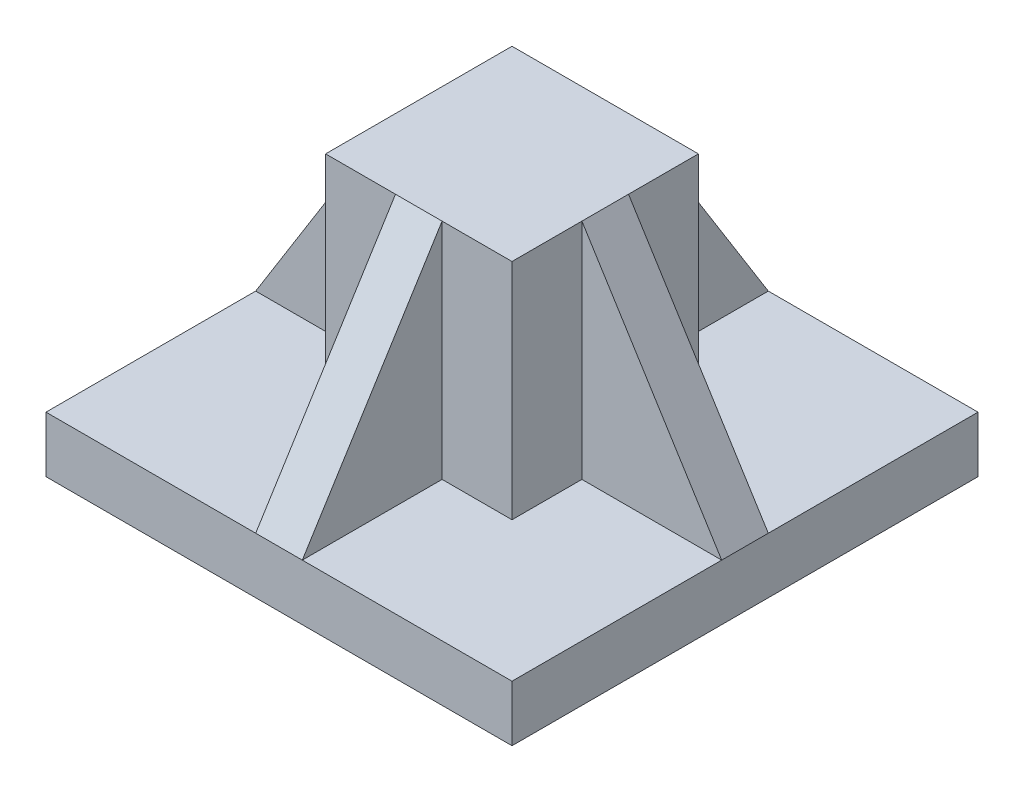
SolidWorks part; units mm, degrees
material "Thornel VCB-20 Carbon Cloth"
ref_plane "Front Plane" through (0, 0, 0) normal (0, 0, 1) x (1, 0, 0)
ref_plane "Top Plane" through (0, 0, 0) normal (0, 1, 0) x (1, 0, 0)
ref_plane "Right Plane" through (0, 0, 0) normal (1, 0, 0) x (0, 0, -1)
sketch "Sketch1" plane through (0, 0, 0) normal (0, 1, 0) x (1, 0, 0)
  line L1 (-20, 20) -> (20, 20)
  line L2 (-20, 20) -> (-20, -20)
  line L3 (-20, -20) -> (20, -20)
  line L4 (20, 20) -> (20, -20)
  line L5 (-20, 20) -> (20, -20) construction
  line L6 (-20, -20) -> (20, 20) construction
  line L7 (-50, 50) -> (50, 50)
  line L8 (-50, 50) -> (-50, -50)
  line L9 (-50, -50) -> (50, -50)
  line L10 (50, 50) -> (50, -50)
  line L11 (-50, 50) -> (50, -50) construction
  line L12 (-50, -50) -> (50, 50) construction
  point P0 (0, 0)
  point P6 (0, 0)
  dimension "D1" = 100
  dimension "D2" = 40
  dimension "D3" = 100
  dimension "D4" = 40
extrude "Boss-Extrude1" add sketch "Sketch1" along normal blind 60 contours L2 L1 L4 L3
extrude "Boss-Extrude2" add sketch "Sketch1<3>" along normal blind 12
sketch "Sketch1<3>" plane through (0, 0, 0) normal (0, 1, 0) x (1, 0, 0) same geometry as "Sketch1"
sketch "Sketch2" plane through (0, 0, 0) normal (0, 0, 1) x (1, 0, 0)
  line L0 (20, 60) -> (50, 12)
  point P4 (0, 0)
  point P6 (0, 0)
rib "Rib1" sketch "Sketch2" sketch "Sketch2" thickness 10 extrusion direction parallel to sketch draft on no parameters "D1"=10
pattern_circular "CirPattern1" count 4 over 360 about axis through (0, 60, 0) along (0, 1, 0) of "Rib1"
